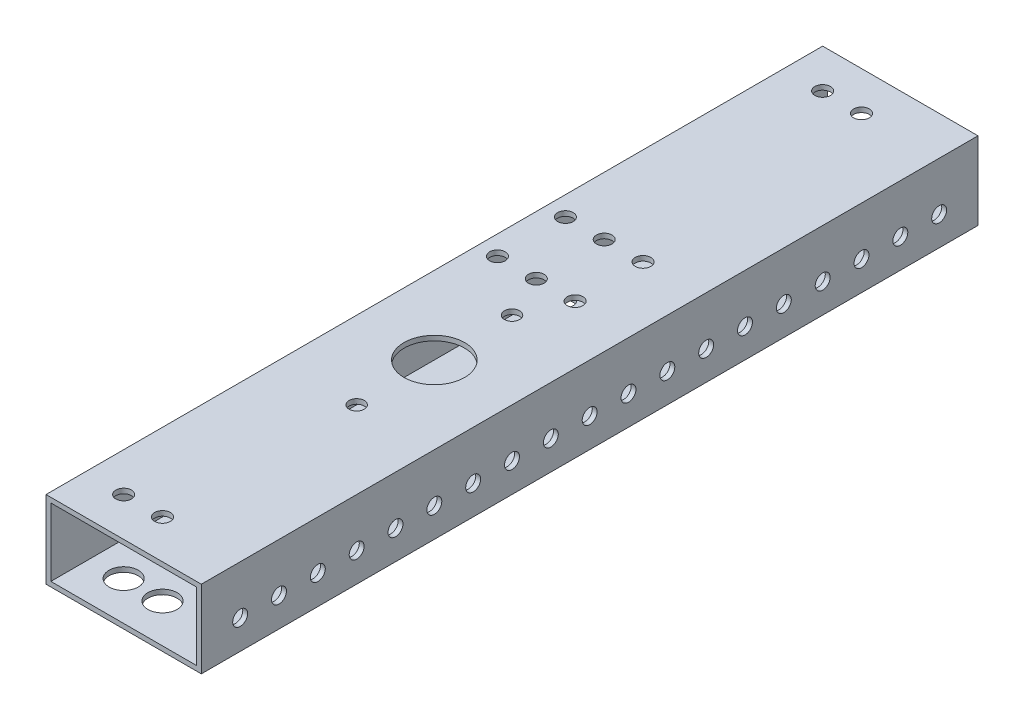
SolidWorks part; units mm, degrees
other "Markup1"
sketch "Sketch7" plane through (25.4, 12.7, -127) normal (0.9965, 0.0171, -0.0817) x (-0.082, 0.0128, -0.9966)
sketch "Sketch8" plane through (25.4, 12.7, -127) normal (0.9965, 0.0171, -0.0817) x (-0.082, 0.0128, -0.9966)
sketch "Sketch9" plane through (25.4, 12.7, -127) normal (0.9965, 0.0171, -0.0817) x (-0.082, 0.0128, -0.9966)
sketch "Sketch12" plane through (25.4, 12.7, -127) normal (0.9965, 0.0171, -0.0817) x (-0.082, 0.0128, -0.9966)
material "6061-T6 (SS)"
ref_plane "Front Plane" through (0, 0, 0) normal (0, 0, 1) x (1, 0, 0)
ref_plane "Top Plane" through (0, 0, 0) normal (0, 1, 0) x (1, 0, 0)
ref_plane "Right Plane" through (0, 0, 0) normal (1, 0, 0) x (0, 0, -1)
sketch "Sketch1" plane through (0, 0, 0) normal (0, 0, 1) x (1, 0, 0)
  line L0 (-23.8125, 11.1125) -> (23.8125, 11.1125)
  line L1 (-25.4, -12.7) -> (25.4, -12.7)
  line L2 (-25.4, -12.7) -> (-25.4, 12.7)
  line L3 (-25.4, 12.7) -> (25.4, 12.7)
  line L4 (25.4, -12.7) -> (25.4, 12.7)
  line L5 (-25.4, -12.7) -> (25.4, 12.7) construction
  line L6 (-25.4, 12.7) -> (25.4, -12.7) construction
  line L7 (23.8125, -11.1125) -> (23.8125, 11.1125)
  line L8 (-23.8125, -11.1125) -> (23.8125, -11.1125)
  line L9 (-23.8125, -11.1125) -> (-23.8125, 11.1125)
  point P0 (0, 0)
  dimension "D1" = 50.8
  dimension "D2" = 25.4
  dimension "D3" = 1.5875
extrude "Boss-Extrude1" add sketch "Sketch1" along normal mid plane 254
sketch "Sketch3" plane through (0, 12.7, 0) normal (0, 1, 0) x (1, 0, 0)
  line L0 (25.4, 127) -> (-25.4, 127) construction
  line L1 (25.4, -127) -> (-25.4, -127) construction
  line L3 (-25.4, -127) -> (-25.4, 127) construction
  line L4 (25.4, -127) -> (25.4, 127) construction
  circle A0 centre (-12.7, -114.3) radius 2.5527
  circle A1 centre (0, -114.3) radius 2.5527
  circle A2 centre (-12.7, 114.3) radius 2.5527
  circle A3 centre (0, 114.3) radius 2.5527
  dimension "D5" = 5.1054
  dimension "D1" = 12.7
  dimension "D2" = 12.7
  dimension "D3" = 12.7
  dimension "D4" = 12.7
  dimension "D6" = 12.7
  dimension "D7" = 12.7
  dimension "D8" = 12.7
  dimension "D9" = 25.4
  dimension "D10" = 12.7
  dimension "D11" = 25.4
extrude "Cut-Extrude1" cut sketch "Sketch3" against normal up to surface (1.5875 mm away) up to face at (0, 11.1125, 0)
sketch "Sketch5" plane through (0, -12.7, 0) normal (0, -1, 0) x (1, 0, 0)
  circle A0 centre (-12.7, -114.3) radius 2.5527 construction
  circle A1 centre (0, -114.3) radius 2.5527 construction
  circle A2 centre (0, 114.3) radius 2.5527 construction
  circle A3 centre (-12.7, 114.3) radius 2.5527 construction
  circle A4 centre (-12.7, -114.3) radius 2.5527
  circle A5 centre (0, -114.3) radius 2.5527
  circle A6 centre (0, 114.3) radius 2.5527
  circle A7 centre (-12.7, 114.3) radius 2.5527
  circle A8 centre (-12.7, 114.3) radius 4.7625
  circle A9 centre (0, 114.3) radius 4.7625
  circle A10 centre (0, -114.3) radius 4.7625
  circle A11 centre (-12.7, -114.3) radius 4.7625
  dimension "D1" = 9.525
extrude "Cut-Extrude2" cut sketch "Sketch5" against normal up to surface (1.5875 mm away) contours A10 A5 | A5 | A11 A4 | A4 | A6 | A9 A6 | A8 A7 | A7 region at (-12.7, -12.7, -114.3) region at (0, -12.7, -114.3) region at (0, -12.7, 114.3) region at (-12.7, -12.7, 114.3) region at (-17.3278, -12.7, 114.3) region at (-4.6278, -12.7, 114.3) region at (-4.6278, -12.7, -114.3) region at (-17.3278, -12.7, -114.3) up to face at (0, -11.1125, 0)
sketch "Sketch6" plane through (25.4, 0, 0) normal (1, 0, 0) x (0, 0, -1)
  line L0 (-127, -12.7) -> (-127, 12.7) construction
  line L1 (-127, -12.7) -> (127, -12.7) construction
  line L2 (0, 12.7) -> (0, -12.7) construction
  line L3 (-127, 12.7) -> (127, 12.7) construction
  circle A0 centre (-114.3, -3.175) radius 2.4384
  circle A1 centre (-101.6, -3.175) radius 2.4384
  circle A2 centre (-88.9, -3.175) radius 2.4384
  circle A3 centre (88.9, -3.175) radius 2.4384
  circle A4 centre (101.6, -3.175) radius 2.4384
  circle A5 centre (114.3, -3.175) radius 2.4384
  circle A6 centre (-76.2, -3.175) radius 2.4384
  circle A7 centre (-63.5, -3.175) radius 2.4384
  circle A8 centre (-50.8, -3.175) radius 2.4384
  circle A9 centre (-38.1, -3.175) radius 2.4384
  circle A10 centre (-25.4, -3.175) radius 2.4384
  circle A11 centre (-12.7, -3.175) radius 2.4384
  circle A12 centre (0, -3.175) radius 2.4384
  circle A13 centre (12.7, -3.175) radius 2.4384
  circle A14 centre (25.4, -3.175) radius 2.4384
  circle A15 centre (38.1, -3.175) radius 2.4384
  circle A16 centre (50.8, -3.175) radius 2.4384
  circle A17 centre (63.5, -3.175) radius 2.4384
  circle A18 centre (76.2, -3.175) radius 2.4384
  dimension "D1" = 4.8768
  dimension "D7" = 4.8768
  dimension "D2" = 12.7
  dimension "D3" = 9.525
  dimension "D4" = 12.7
  dimension "D5" = 12.7
  dimension "D6" = 12.7
  dimension "D8" = 9.525
  dimension "D10" = 12.7
  dimension "D9" = 13
extrude "Cut-Extrude3" cut sketch "Sketch6" against normal up to surface (1.5875 mm away) contours A5 | A4 | A3 | A0 | A1 | A2 | A6 | A7 | A8 | A9 | A10 | A11 | A12 L2 | L2 A12 | A13 | A14 | A15 | A16 | A17 | A18 | A12 region at (25.4, -3.175, -1.0349) region at (25.4, -3.175, 1.0349) region at (25.4, -3.175, 114.3) region at (25.4, -3.175, 101.6) region at (25.4, -3.175, 88.9) region at (25.4, -3.175, -88.9) region at (25.4, -3.175, -101.6) region at (25.4, -3.175, -114.3) region at (25.4, -3.175, 76.2) region at (25.4, -3.175, 63.5) region at (25.4, -3.175, 50.8) region at (25.4, -3.175, 38.1) region at (25.4, -3.175, 25.4) region at (25.4, -3.175, 12.7) region at (25.4, -3.175, -12.7) region at (25.4, -3.175, -25.4) region at (25.4, -3.175, -38.1) region at (25.4, -3.175, -50.8) region at (25.4, -3.175, -63.5) region at (25.4, -3.175, -76.2) up to face at (23.8125, 0, 0)
sketch "Sketch11" plane through (0, 12.7, 0) normal (0, 1, 0) x (1, 0, 0)
  line L0 (-25.4, -127) -> (-25.4, 127) construction
  line L2 (0, 0) -> (0, -50.8) construction
  line L3 (25.4, 127) -> (-25.4, 127) construction
  line L5 (-19.05, 36.5125) -> (6.35, 36.5125) construction
  line L6 (-19.05, 36.5125) -> (-19.05, 14.2875) construction
  line L7 (-19.05, 14.2875) -> (6.35, 14.2875) construction
  line L8 (6.35, 36.5125) -> (6.35, 14.2875) construction
  line L9 (-19.05, 36.5125) -> (6.35, 14.2875) construction
  line L10 (-19.05, 14.2875) -> (6.35, 36.5125) construction
  circle A0 centre (0, -25.4) radius 9.906
  circle A1 centre (0, 0) radius 2.4892
  circle A2 centre (0, -50.8) radius 2.4892
  circle A3 centre (6.35, 14.2875) radius 2.5527
  circle A4 centre (-19.05, 14.2875) radius 2.5527
  circle A5 centre (-19.05, 36.5125) radius 2.5527
  circle A6 centre (6.35, 36.5125) radius 2.5527
  circle A7 centre (-6.35, 14.2875) radius 2.5527
  circle A8 centre (-6.35, 36.5125) radius 2.5527
  point P2 (0, -25.4)
  point P8 (-6.35, 25.4)
  dimension "D1" = 19.812
  dimension "D3" = 4.9784
  dimension "D4" = 25.4
  dimension "D5" = 5.1054
  dimension "D6" = 25.4
  dimension "D7" = 22.225
  dimension "D2" = 152.4
  dimension "D8" = 101.6
  dimension "D9" = 6.35
extrude "Cut-Extrude4" cut sketch "Sketch11" against normal through all
